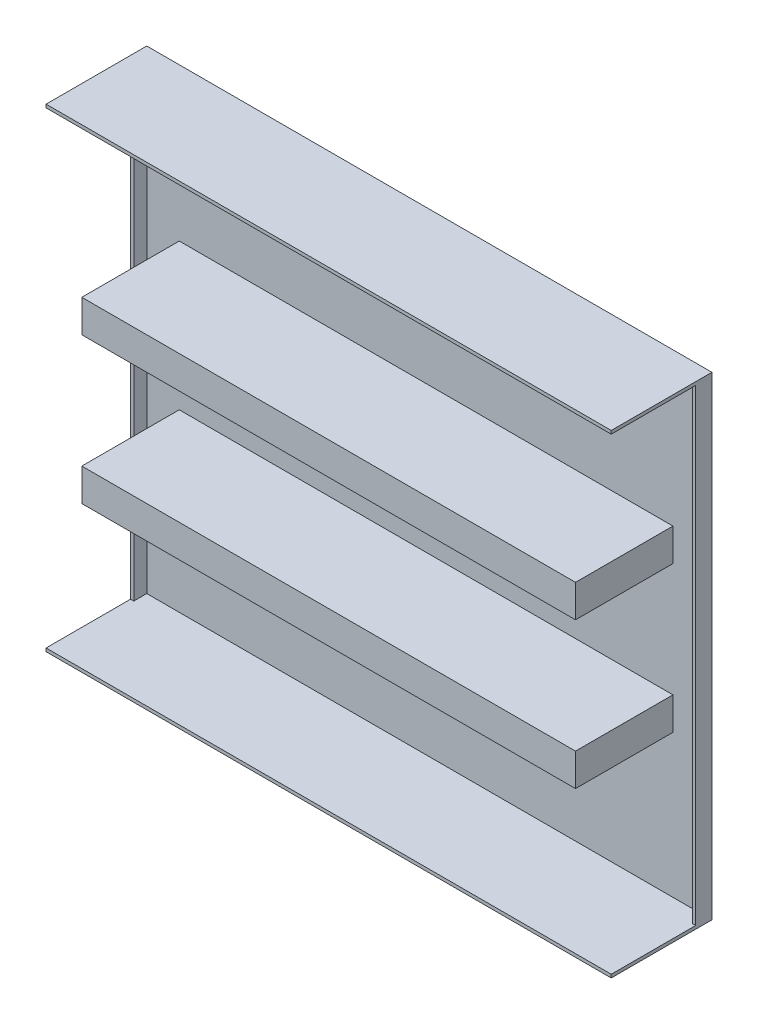
SolidWorks part; units mm, degrees
ref_plane "Płaszczyzna przednia" through (0, 0, 0) normal (0, 0, 1) x (1, 0, 0)
ref_plane "Płaszczyzna górna" through (0, 0, 0) normal (0, 1, 0) x (1, 0, 0)
ref_plane "Płaszczyzna prawa" through (0, 0, 0) normal (1, 0, 0) x (0, 0, -1)
sketch "Szkic1" plane through (0, 0, 0) normal (0, 0, 1) x (1, 0, 0)
  line L0 (0, 0) -> (172, 0)
  line L1 (172, 0) -> (172, 144)
  line L2 (0, 0) -> (0, 144)
  line L3 (0, 144) -> (172, 144)
  line L9 (-1, 145) -> (173, 145)
  line L10 (-1, 145) -> (-1, -1)
  line L11 (-1, -1) -> (173, -1)
  line L12 (173, 145) -> (173, -1)
  point P4 (0, 0)
  point P6 (0, 0)
  dimension "D1" = 144
  dimension "D2" = 172
extrude "Dodanie-wyciągnięcie1" add sketch "Szkic1" along normal blind 1 contours L3 L1 L0 L2
extrude "Dodanie-wyciągnięcie2" add sketch "Szkic1<3>" along normal blind 5 contours L3 L1 L0 L2 | L9 L12 L11 L10
sketch "Szkic1<3>" plane through (0, 0, 0) normal (0, 0, 1) x (1, 0, 0) same geometry as "Szkic1"
sketch "Szkic2" plane through (0, 0, 1) normal (0, 0, 1) x (1, 0, 0)
  line L0 (0, 144) -> (0, 99)
  line L1 (0, 0) -> (0, 144) construction
  line L2 (0, 99) -> (0, 89)
  line L3 (172, 0) -> (172, 144) construction
  line L4 (0, 99) -> (172, 99)
  line L5 (0, 99) -> (0, 89)
  line L6 (0, 89) -> (172, 89)
  line L7 (172, 99) -> (172, 89)
  line L8 (10, 94) -> (10, 49)
  line L9 (0, 99) -> (10, 99)
  line L10 (0, 99) -> (0, 89)
  line L11 (0, 89) -> (10, 89)
  line L12 (10, 99) -> (10, 89)
  line L13 (172, 99) -> (162, 99)
  line L14 (172, 99) -> (172, 89)
  line L15 (172, 89) -> (162, 89)
  line L16 (162, 99) -> (162, 89)
  line L17 (10, 54) -> (10, 44)
  line L19 (10, 44) -> (162, 44)
  line L20 (10, 44) -> (10, 54)
  line L21 (10, 54) -> (162, 54)
  line L22 (162, 44) -> (162, 54)
  circle A0 centre (10, 49) radius 5
  dimension "D6" = 10
  dimension "D1" = 45
  dimension "D2" = 10
  dimension "D3" = 10
  dimension "D4" = 10
  dimension "D5" = 45
extrude "Dodanie-wyciągnięcie4" add sketch "Szkic2" along normal blind 30 contours L4 L6 L7 | L20 L19 L22 L21 region at (86, 94, 1)
sketch "Szkic4" plane through (0, 0, 5) normal (0, 0, 1) x (1, 0, 0)
  line L0 (173, 145) -> (173, -1) construction
  line L1 (-1, -1) -> (173, -1)
  line L2 (-1, -1) -> (-1, 0)
  line L3 (-1, 0) -> (173, 0)
  line L4 (173, -1) -> (173, 0)
  line L6 (-1, 145) -> (173, 145)
  line L7 (-1, 145) -> (-1, 144)
  line L8 (-1, 144) -> (173, 144)
  line L9 (173, 145) -> (173, 144)
extrude "Dodanie-wyciągnięcie5" add sketch "Szkic4" along normal blind 26
